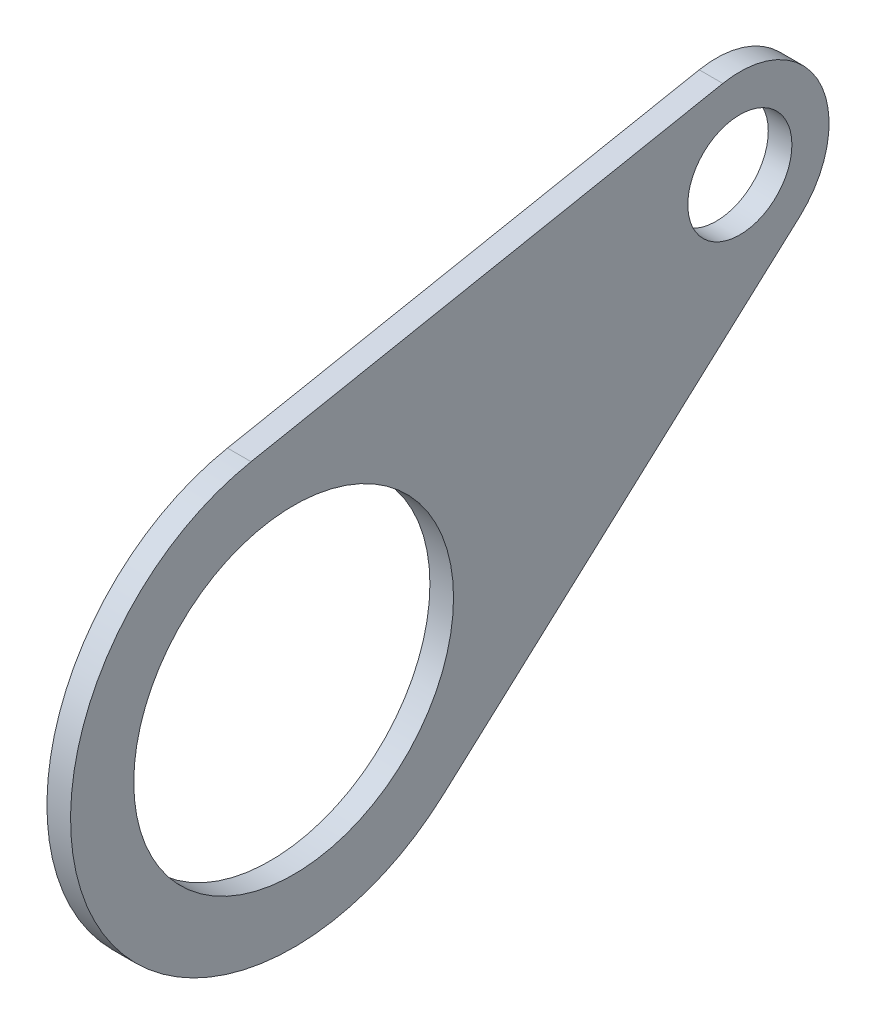
SolidWorks part; units mm, degrees
ref_plane "Front Plane" through (0, 0, 0) normal (0, 0, 1) x (1, 0, 0)
ref_plane "Top Plane" through (0, 0, 0) normal (0, 1, 0) x (1, 0, 0)
ref_plane "Right Plane" through (0, 0, 0) normal (1, 0, 0) x (0, 0, -1)
sketch "Sketch1" plane through (0, 0, 0) normal (1, 0, 0) x (0, 0, -1)
  line L0 (-5.7244, 29.4488) -> (57.7102, 41.7795)
  line L1 (0, 0) -> (60, 30) construction
  line L3 (20.1244, -22.2488) -> (68.0498, 21.1005)
  circle A0 centre (0, 0) radius 21.5
  circle A1 centre (60, 30) radius 7
  arc A2 (-5.7244, 29.4488) -> (20.1244, -22.2488) centre (0, 0) ccw
  arc A3 (68.0498, 21.1005) -> (57.7102, 41.7795) centre (60, 30) ccw
  dimension "D1" = 43
  dimension "D2" = 60
  dimension "D4" = 14
  dimension "D3" = 24
  dimension "D5" = 60
  dimension "D6" = 30
extrude "Boss-Extrude1" add sketch "Sketch1" along normal blind 3.175
